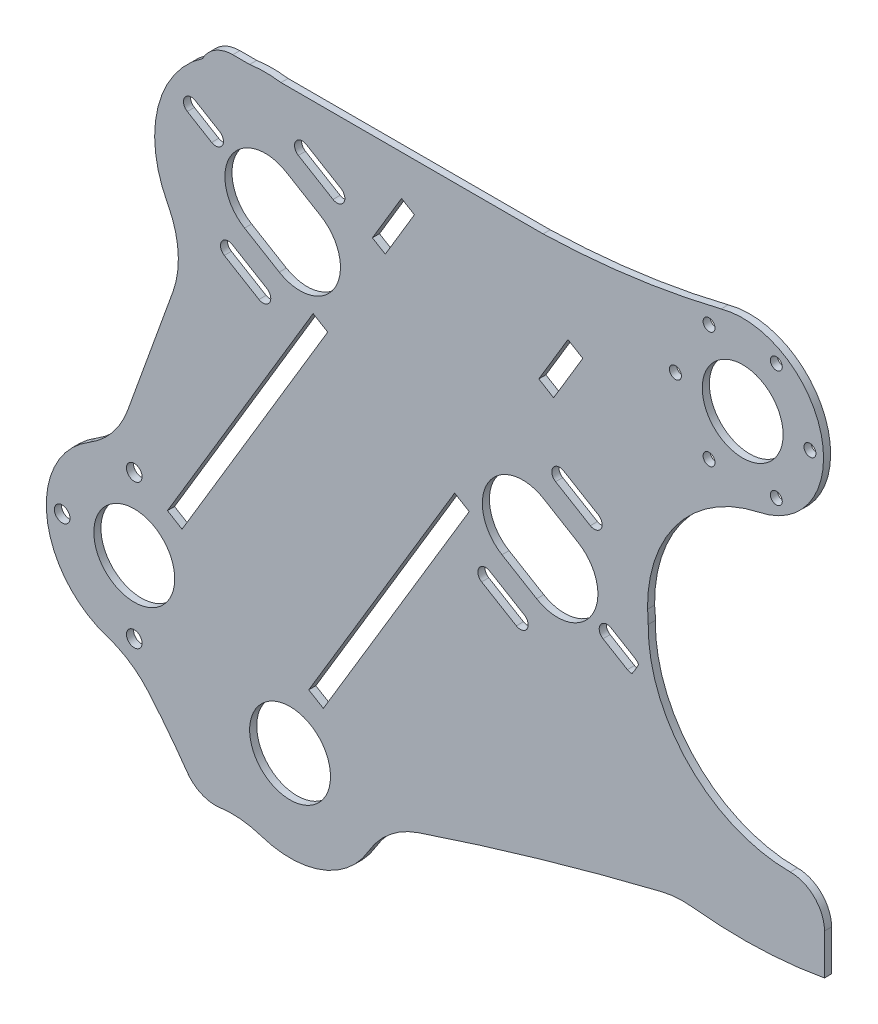
SolidWorks part; units mm, degrees
ref_plane "Plano frontal" through (0, 0, 0) normal (0, 0, 1) x (1, 0, 0)
ref_plane "Plano superior" through (0, 0, 0) normal (0, 1, 0) x (1, 0, 0)
ref_plane "Plano direito" through (0, 0, 0) normal (1, 0, 0) x (0, 0, -1)
sketch "Esboço1" plane through (0, 0, 0) normal (0, 0, 1) x (1, 0, 0)
  line L0 (49.9, 342) -> (-3.2758, 342)
  line L1 (49.9, 380) -> (-110.1, 380)
  line L3 (-3.2758, 342) -> (-3.2758, 208.9035)
  arc A0 (49.9, 342) -> (49.9, 380) centre (49.9, 361) ccw
  arc A1 (-110.1, 380) -> (-3.2758, 208.9035) centre (49.9, 361) ccw
  circle A2 centre (49.9, 361) radius 14.25
  dimension "D1" = 28.5
  dimension "D2" = 160
extrude "Ressalto-extrusão1" add sketch "Esboço1" along normal blind 2.5
sketch "Esboço2" plane through (0, 0, 2.5) normal (0, 0, 1) x (1, 0, 0)
  line L0 (-80.4635, 317.1268) -> (-48.9925, 362.4233)
  line L2 (-53.7045, 365.8323) -> (-85.3921, 320.5779)
  line L3 (-85.3921, 320.5779) -> (-80.4635, 317.1268)
  line L4 (49.9, 380) -> (-110.1, 380) construction
  line L5 (-53.7045, 365.8323) -> (-56.2781, 367.6942)
  line L6 (-56.2781, 367.6942) -> (-47.4451, 368.6891)
  line L7 (-47.4451, 368.6891) -> (-46.4607, 359.9499)
  line L8 (-46.4607, 359.9499) -> (-48.9925, 362.4233)
  line L9 (-51.3485, 364.1278) -> (-47.4451, 368.6891) construction
  line L10 (-53.7045, 365.8323) -> (-48.9925, 362.4233) construction
  dimension "D1" = 55
extrude "Corte-extrusão1" [suppressed] cut sketch "Esboço2" against normal blind 6
sketch "Esboço3" plane through (0, 0, 2.5) normal (0, 0, 1) x (1, 0, 0)
  line L0 (-3.2758, 208.9035) -> (-3.2758, 342) construction
  line L1 (78.7242, 230.9832) -> (78.7242, 202.475)
  line L2 (-3.2758, 208.9035) -> (-3.2758, 238.9035)
  arc A0 (-3.2758, 238.9035) -> (78.7242, 230.9832) centre (49.9, 361) ccw
  arc A1 (-3.2758, 208.9035) -> (78.7242, 202.475) centre (49.9, 361) ccw
  dimension "D1" = 82
  dimension "D2" = 30
extrude "Ressalto-extrusão2" add sketch "Esboço3" against normal blind 2.5
sketch "Esboço5" plane through (0, 0, 2.5) normal (0, 0, 1) x (1, 0, 0)
  line L0 (-110.1, 380) -> (-141.9313, 380)
  line L1 (-141.9313, 380) -> (-141.2627, 323.7246)
  line L2 (-186.8216, 197.6391) -> (-141.2627, 323.7246)
  line L7 (49.9, 380) -> (-110.1, 380)
  line L8 (78.7242, 202.475) -> (78.7242, 230.9832)
  line L9 (-3.2758, 238.9035) -> (-3.2758, 342)
  line L10 (-3.2758, 342) -> (49.9, 342)
  arc A0 (-186.8216, 197.6391) -> (-141.2627, 146.1998) centre (-333.9706, 21.4169) cw
  arc A2 (-141.2627, 146.1998) -> (27.0633, 201.5024) centre (279.6298, -851.0608) cw
  arc A3 (-110.1, 380) -> (78.7242, 202.475) centre (49.9, 361) ccw construction
  arc A7 (49.9, 342) -> (49.9, 380) centre (49.9, 361) ccw
  arc A8 (-110.1, 380) -> (78.7242, 202.475) centre (49.9, 361) ccw
  arc A9 (-3.2758, 238.9035) -> (78.7242, 230.9832) centre (49.9, 361) ccw
  arc A11 (-110.1, 380) -> (27.0633, 201.5024) centre (49.9, 361) ccw
  arc M10 (-110.1, 380) -> (78.7242, 202.475) centre (49.9, 361) ccw
  dimension "D1" = 0
extrude "Ressalto-extrusão3" add sketch "Esboço5" against normal blind 2.5 contours A0 A2 L0 L1 L2 M10 region at (-109.9694, 237.9744, 2.5)
sketch "Esboço6" plane through (0, 0, 2.5) normal (0, 0, 1) x (1, 0, 0)
  line L0 (-118.3294, 341.3928) -> (-15.3825, 279.7331) construction
  line L1 (-164.5132, 209.792) -> (-109.6082, 176.9068) construction
  line L2 (-66.8559, 310.563) -> (-137.0607, 193.3494) construction
  circle A0 centre (-118.3294, 341.3928) radius 14.25
  circle A1 centre (-15.3825, 279.7331) radius 14.25
  circle A2 centre (-164.5132, 209.792) radius 14.25
  circle A3 centre (-109.6082, 176.9068) radius 14.25
  dimension "D1" = 28.5
  dimension "D2" = 28.5
  dimension "D3" = 28.5
  dimension "D4" = 28.5
  dimension "D5" = 120
  dimension "D6" = 64
extrude "Corte-extrusão2" cut sketch "Esboço6" against normal through all
sketch "Esboço7" plane through (0, 0, 2.5) normal (0, 0, 1) x (1, 0, 0)
  line L0 (-164.5132, 209.792) -> (-109.6082, 176.9068) construction
  line L1 (-109.6082, 176.9068) -> (-37.0028, 298.1283) construction
  line L2 (-164.5132, 209.792) -> (-93.0231, 329.1516) construction
sketch "Esboço8" plane through (0, 0, 2.5) normal (0, 0, 1) x (1, 0, 0)
  circle A0 centre (-164.5132, 209.792) radius 24.626
  circle A1 centre (-164.5132, 209.792) radius 14.25
extrude "Ressalto-extrusão4" add sketch "Esboço8" against normal blind 2.5
fillet "Filete1" radius 12 1 edges at (-174.2585, 232.4077, 1.25)
fillet "Filete2" radius 12 3 edges at (-141.9313, 380, 1.25) (-141.2627, 323.7246, 1.25) (-3.2758, 238.9035, 1.25)
fillet "Filete3" radius 12 1 edges at (78.7242, 230.9832, 1.25)
fillet "Filete4" radius 12 1 edges at (-3.2758, 342, 1.25)
sketch "Esboço9" plane through (0, 0, 2.5) normal (0, 0, 1) x (1, 0, 0)
  circle A0 centre (-118.3294, 341.3928) radius 25.4 construction
  circle A1 centre (-164.5132, 209.792) radius 25.4 construction
  circle A2 centre (-118.3294, 341.3928) radius 39
  circle A3 centre (-164.5132, 209.792) radius 31
  circle A4 centre (-118.3294, 341.3928) radius 14.25
  circle A5 centre (-164.5132, 209.792) radius 14.25
  circle A7 centre (-118.3294, 341.3928) radius 14.25 construction
  dimension "D1" = 50.8
  dimension "D2" = 50.8
  dimension "D3" = 78
  dimension "D4" = 62
extrude "Ressalto-extrusão5" add sketch "Esboço9" against normal blind 2.5
sketch "Esboço10" plane through (0, 0, 2.5) normal (0, 0, 1) x (1, 0, 0)
  circle A0 centre (-164.5132, 209.792) radius 25.4 construction
  circle A6 centre (-189.9132, 209.792) radius 2.75
  circle A7 centre (-164.5132, 235.192) radius 2.75
  circle A8 centre (-139.1132, 209.792) radius 2.75
  circle A9 centre (-164.5132, 184.392) radius 2.75
  dimension "D1" = 50.8
extrude "Corte-extrusão3" cut sketch "Esboço10" against normal through all
sketch "Esboço11" plane through (0, 0, 2.5) normal (0, 0, 1) x (1, 0, 0)
  line L0 (-87.028, 319.847) -> (-48.9851, 297.4774) construction
  line L1 (-68.0065, 308.6622) -> (-136.137, 192.7962) construction
  line L2 (-164.5132, 209.792) -> (-109.6082, 176.9068) construction
  line L3 (-87.028, 319.847) -> (-155.9343, 204.6537)
  line L4 (-48.9851, 297.4774) -> (-118.1871, 182.0451)
  circle A0 centre (-118.3294, 341.3928) radius 38 construction
  circle A1 centre (-15.3825, 279.7331) radius 38 construction
  circle A2 centre (-164.5132, 209.792) radius 10
  circle A3 centre (-109.6082, 176.9068) radius 10
  dimension "D1" = 76
  dimension "D2" = 76
  dimension "D3" = 20
  dimension "D4" = 20
sketch "Esboço12" plane through (0, 0, 2.5) normal (0, 0, 1) x (1, 0, 0)
  circle A0 centre (-109.6082, 176.9068) radius 32
  circle A1 centre (-109.6082, 176.9068) radius 14.25
  circle A2 centre (-15.3825, 279.7331) radius 32
  circle A3 centre (-15.3825, 279.7331) radius 14.25
  dimension "D1" = 64
  dimension "D2" = 64
extrude "Ressalto-extrusão6" add sketch "Esboço12" against normal blind 2.5
sketch "Esboço13" plane through (0, 0, 2.5) normal (0, 0, 1) x (1, 0, 0)
  line L0 (-144.2405, 224.2027) -> (-92.9058, 310.0208) construction
  line L1 (-144.2405, 224.2027) -> (-147.6732, 226.256) construction
  line L2 (-92.9058, 310.0208) -> (-96.3386, 312.0742) construction
  line L3 (-147.6732, 226.256) -> (-96.3386, 312.0742) construction
  line L4 (-87.028, 319.847) -> (-155.9343, 204.6537) construction
  line L5 (-55.0433, 287.3721) -> (-106.4615, 201.604) construction
  line L6 (-55.0433, 287.3721) -> (-51.6125, 285.3154) construction
  line L7 (-106.4615, 201.604) -> (-103.0307, 199.5473) construction
  line L8 (-51.6125, 285.3154) -> (-103.0307, 199.5473) construction
  line L9 (-48.9851, 297.4774) -> (-118.1871, 182.0451) construction
  line L10 (-144.2405, 224.2027) -> (-106.4615, 201.604) construction
  line L11 (-96.3386, 312.0742) -> (-147.6732, 226.256)
  line L12 (-96.3386, 312.0742) -> (-101.4877, 315.1543)
  line L13 (-147.6732, 226.256) -> (-152.8223, 229.3361)
  line L14 (-101.4877, 315.1543) -> (-152.8223, 229.3361)
  line L15 (-103.0307, 199.5473) -> (-51.6125, 285.3154)
  line L16 (-103.0307, 199.5473) -> (-97.8846, 196.4622)
  line L17 (-51.6125, 285.3154) -> (-46.4664, 282.2303)
  line L18 (-97.8846, 196.4622) -> (-46.4664, 282.2303)
  dimension "D1" = 100
  dimension "D2" = 100
  dimension "D3" = 4
  dimension "D4" = 4
  dimension "D5" = 6
  dimension "D6" = 6
extrude "Corte-extrusão4" cut sketch "Esboço13" against normal blind 6
sketch "Esboço14" plane through (0, 0, 2.5) normal (0, 0, 1) x (1, 0, 0)
  circle A0 centre (-139.1132, 209.792) radius 2.75
extrude "Ressalto-extrusão7" add sketch "Esboço14" against normal blind 2.5
sketch "Esboço15" plane through (0, 0, 0) normal (0, 0, -1) x (-1, 0, 0)
  line L0 (6.4459, 348.9866) -> (16.7295, 331.8329)
  line L1 (6.4459, 348.9866) -> (11.6764, 352.1222)
  line L2 (16.7295, 331.8329) -> (21.96, 334.9686)
  line L3 (11.6764, 352.1222) -> (21.96, 334.9686)
  line L4 (65.7809, 363.1587) -> (76.0478, 345.995)
  line L5 (65.7809, 363.1587) -> (70.3295, 365.8796)
  line L6 (76.0478, 345.995) -> (80.5964, 348.7159)
  line L7 (70.3295, 365.8796) -> (80.5964, 348.7159)
extrude "Corte-extrusão5" cut sketch "Esboço15" against normal blind 10
sketch "Esboço16" plane through (0, 0, 2.5) normal (0, 0, 1) x (1, 0, 0)
  circle A0 centre (49.9, 361) radius 28.5
  circle A1 centre (49.9, 361) radius 14.25
  dimension "D1" = 57
extrude "Ressalto-extrusão8" add sketch "Esboço16" against normal blind 2.5
fillet "Filete6" radius 12 2 edges at (28.6574, 342, 1.25) (28.6574, 380, 1.25)
sketch "Esboço17" plane through (0, 0, 0) normal (0, 0, -1) x (-1, 0, 0)
  circle A0 centre (15.3825, 279.7331) radius 25.4 construction
  circle A1 centre (118.3294, 341.3928) radius 25.4 construction
  circle A2 centre (15.3825, 305.1331) radius 2.75
  circle A3 centre (-10.0175, 279.7331) radius 2.75
  circle A4 centre (15.3825, 254.3331) radius 2.75
  circle A5 centre (40.7825, 279.7331) radius 2.75
  circle A6 centre (118.3294, 366.7928) radius 2.75
  circle A7 centre (92.9294, 341.3928) radius 2.75
  circle A8 centre (118.3294, 315.9928) radius 2.75
  circle A9 centre (143.7294, 341.3928) radius 2.75
  dimension "D1" = 50.8
  dimension "D2" = 50.8
  dimension "D3" = 5.5
  dimension "D4" = 5.5
  dimension "D5" = 5.5
  dimension "D6" = 5.5
  dimension "D7" = 5.5
extrude "Corte-extrusão6" [suppressed] cut sketch "Esboço17" against normal blind 2.5
fillet "Filete7" radius 32 6 edges at (27.0633, 201.5024, 1.25) (-78.255, 170.5054, 1.25) (-128.8584, 151.3446, 1.25) (-166.9045, 178.8844, 1.25) (-171.5187, 239.9901, 1.25) (-145.1196, 313.0506, 1.25)
fillet "Filete8" radius 12 1 edges at (-3.2758, 250.1117, 1.25)
fillet "Filete9" radius 12 1 edges at (-3.2758, 309.3545, 1.25)
fillet "Filete10" radius 12 1 edges at (-141.2627, 146.1998, 1.25)
sketch "Esboço18" plane through (0, 0, 2.5) normal (0, 0, 1) x (1, 0, 0)
  circle A0 centre (38.05, 381.5248) radius 2.1
  circle A1 centre (61.75, 381.5248) radius 2.1
  circle A2 centre (73.6, 361) radius 2.1
  circle A3 centre (26.2, 361) radius 2.1
  circle A4 centre (38.05, 340.4752) radius 2.1
  circle A5 centre (61.75, 340.4752) radius 2.1
extrude "Corte-extrusão7" cut sketch "Esboço18" against normal through all
sketch "Esboço19" plane through (0, 0, 2.5) normal (0, 0, 1) x (1, 0, 0)
  line L0 (-118.3294, 341.3928) -> (-15.3825, 279.7331) construction
  line L1 (-118.3294, 341.3928) -> (-106.1044, 334.0707) construction
  line L2 (-111.0073, 353.6178) -> (-98.7823, 346.2957)
  line L3 (-125.6515, 329.1679) -> (-113.4265, 321.8458)
  line L4 (-15.3825, 279.7331) -> (-27.6074, 287.0552) construction
  line L5 (-22.7046, 267.5081) -> (-34.9295, 274.8302)
  line L6 (-8.0604, 291.958) -> (-20.2853, 299.2801)
  circle A0 centre (-118.3294, 341.3928) radius 14.25 construction
  arc A1 (-111.0073, 353.6178) -> (-125.6515, 329.1679) centre (-118.3294, 341.3928) ccw
  arc A2 (-113.4265, 321.8458) -> (-98.7823, 346.2957) centre (-106.1044, 334.0707) ccw
  circle A3 centre (-15.3825, 279.7331) radius 14.25 construction
  arc A4 (-22.7046, 267.5081) -> (-8.0604, 291.958) centre (-15.3825, 279.7331) ccw
  arc A5 (-20.2853, 299.2801) -> (-34.9295, 274.8302) centre (-27.6074, 287.0552) ccw
  point P4 (-112.2169, 337.7318)
  point P12 (-21.4949, 283.3941)
extrude "Corte-extrusão8" cut sketch "Esboço19" against normal blind 10
sketch "Esboço21" plane through (0, 0, 2.5) normal (0, 0, 1) x (1, 0, 0)
  arc A0 (16.6148, 279.3142) -> (66.6745, 228.8045) centre (66.468, 278.6615) ccw
  arc A1 (1.4429, 252.5134) -> (2.1497, 306.5029) centre (-15.3825, 279.7331) ccw construction
  arc A2 (78.7242, 216.8046) -> (65.3336, 228.7237) centre (66.7242, 216.8046) ccw construction
  arc A3 (1.4429, 252.5134) -> (16.6148, 279.3142) centre (-15.3825, 279.7331) ccw
  arc A4 (1.4429, 252.5134) -> (4.6466, 235.7509) centre (1.3973, 243.8173) ccw
  arc A5 (4.6466, 235.7509) -> (66.6745, 228.8045) centre (45.9194, 323.8842) ccw
sketch "Esboço20" plane through (0, 0, 2.5) normal (0, 0, 1) x (1, 0, 0)
  line L0 (-118.3294, 341.3928) -> (-106.1044, 334.0707) construction
  line L1 (-105.2781, 363.1833) -> (-93.0531, 355.8612) construction
  line L2 (-131.3807, 319.6024) -> (-119.1558, 312.2803) construction
  line L3 (-105.2781, 363.1833) -> (-93.0531, 355.8612) construction
  line L4 (-103.865, 365.5425) -> (-91.6401, 358.2204)
  line L5 (-106.6911, 360.8241) -> (-94.4662, 353.502)
  line L6 (-144.4093, 357.0133) -> (-135.8304, 351.875) construction
  line L7 (-142.9962, 359.3725) -> (-134.4173, 354.2342)
  line L8 (-145.8223, 354.6541) -> (-137.2434, 349.5158)
  line L9 (-131.3807, 319.6024) -> (-119.1558, 312.2803) construction
  line L10 (-129.9677, 321.9616) -> (-117.7427, 314.6395)
  line L11 (-132.7937, 317.2432) -> (-120.5688, 309.9211)
  line L12 (-122.0059, 269.1651) -> (-77.3216, 242.4313) construction
  line L13 (-147.6732, 226.256) -> (-96.3386, 312.0742) construction
  line L14 (-51.6125, 285.3154) -> (-103.0307, 199.5473) construction
  line L15 (-99.6638, 255.7982) -> (-73.9869, 298.7159) construction
  line L16 (10.6794, 264.2266) -> (2.0955, 269.3565) construction
  line L17 (12.0902, 266.5872) -> (3.5062, 271.7171)
  line L18 (9.2687, 261.866) -> (0.6848, 266.9959)
  line L19 (-28.4457, 258.0183) -> (-40.6778, 265.3284) construction
  line L20 (-27.035, 260.3789) -> (-39.2671, 267.689)
  line L21 (-29.8564, 255.6577) -> (-42.0886, 262.9678)
  line L22 (-2.3858, 301.6247) -> (-14.6179, 308.9348) construction
  line L23 (-0.9751, 303.9853) -> (-13.2072, 311.2954)
  line L24 (-3.7965, 299.2641) -> (-16.0286, 306.5742)
  arc A1 (-105.2781, 363.1833) -> (-131.3807, 319.6024) centre (-118.3294, 341.3928) ccw construction
  arc A2 (-119.1558, 312.2803) -> (-93.0531, 355.8612) centre (-106.1044, 334.0707) ccw construction
  arc A4 (-103.865, 365.5425) -> (-106.6911, 360.8241) centre (-105.2781, 363.1833) ccw
  arc A5 (-94.4662, 353.502) -> (-91.6401, 358.2204) centre (-93.0531, 355.8612) ccw
  arc A6 (-142.9962, 359.3725) -> (-145.8223, 354.6541) centre (-144.4093, 357.0133) ccw
  arc A7 (-137.2434, 349.5158) -> (-134.4173, 354.2342) centre (-135.8304, 351.875) ccw
  arc A8 (-129.9677, 321.9616) -> (-132.7937, 317.2432) centre (-131.3807, 319.6024) ccw
  arc A9 (-120.5688, 309.9211) -> (-117.7427, 314.6395) centre (-119.1558, 312.2803) ccw
  arc A10 (12.0902, 266.5872) -> (9.2687, 261.866) centre (10.6794, 264.2266) cw
  arc A11 (0.6848, 266.9959) -> (3.5062, 271.7171) centre (2.0955, 269.3565) cw
  arc A12 (-27.035, 260.3789) -> (-29.8564, 255.6577) centre (-28.4457, 258.0183) cw
  arc A13 (-42.0886, 262.9678) -> (-39.2671, 267.689) centre (-40.6778, 265.3284) cw
  arc A14 (-0.9751, 303.9853) -> (-3.7965, 299.2641) centre (-2.3858, 301.6247) cw
  arc A15 (-16.0286, 306.5742) -> (-13.2072, 311.2954) centre (-14.6179, 308.9348) cw
  point P3 (-112.2169, 337.7318)
  point P12 (-99.1656, 359.5222)
  point P17 (-140.1198, 354.4442)
  point P26 (-125.2682, 315.9414)
  point P41 (6.3875, 266.7915)
  point P48 (-34.5618, 261.6733)
  point P55 (-8.5019, 305.2798)
  dimension "D1" = 25.4
  dimension "D2" = 2.75
  dimension "D4" = 2.75
  dimension "D5" = 2.75
  dimension "D3" = 10
extrude "Corte-extrusão9" cut sketch "Esboço20" against normal blind 10
extrude "Ressalto-extrusão9" add sketch "Esboço21" against normal blind 2.5
sketch "Esboço22" plane through (0, 0, 0) normal (0, 0, 1) x (1, 0, 0)
  line L0 (-118.3294, 341.3928) -> (-106.1044, 334.0707) construction
  line L1 (-105.2781, 363.1833) -> (-93.0531, 355.8612) construction
  line L2 (-131.3807, 319.6024) -> (-119.1558, 312.2803) construction
  line L3 (-105.2781, 363.1833) -> (-93.0531, 355.8612) construction
  line L4 (-103.865, 365.5425) -> (-91.6401, 358.2204)
  line L5 (-106.6911, 360.8241) -> (-94.4662, 353.502)
  line L6 (-144.4093, 357.0133) -> (-135.8304, 351.875) construction
  line L7 (-142.9962, 359.3725) -> (-134.4173, 354.2342)
  line L8 (-145.8223, 354.6541) -> (-137.2434, 349.5158)
  line L9 (-131.3807, 319.6024) -> (-119.1558, 312.2803) construction
  line L10 (-129.9677, 321.9616) -> (-117.7427, 314.6395)
  line L11 (-132.7937, 317.2432) -> (-120.5688, 309.9211)
  line L12 (-122.0059, 269.1651) -> (-77.3216, 242.4313) construction
  line L15 (-99.6638, 255.7982) -> (-73.9869, 298.7159) construction
  line L16 (10.6794, 264.2266) -> (2.0955, 269.3565) construction
  line L17 (12.0902, 266.5872) -> (3.5062, 271.7171)
  line L18 (9.2687, 261.866) -> (0.6848, 266.9959)
  line L19 (-28.4457, 258.0183) -> (-40.6778, 265.3284) construction
  line L20 (-27.035, 260.3789) -> (-39.2671, 267.689)
  line L21 (-29.8564, 255.6577) -> (-42.0886, 262.9678)
  line L22 (-2.3858, 301.6247) -> (-14.6179, 308.9348) construction
  line L23 (-0.9751, 303.9853) -> (-13.2072, 311.2954)
  line L24 (-3.7965, 299.2641) -> (-16.0286, 306.5742)
  arc A1 (-105.2781, 363.1833) -> (-131.3807, 319.6024) centre (-118.3294, 341.3928) ccw construction
  arc A2 (-119.1558, 312.2803) -> (-93.0531, 355.8612) centre (-106.1044, 334.0707) ccw construction
  arc A4 (-103.865, 365.5425) -> (-106.6911, 360.8241) centre (-105.2781, 363.1833) ccw
  arc A5 (-94.4662, 353.502) -> (-91.6401, 358.2204) centre (-93.0531, 355.8612) ccw
  arc A6 (-142.9962, 359.3725) -> (-145.8223, 354.6541) centre (-144.4093, 357.0133) ccw
  arc A7 (-137.2434, 349.5158) -> (-134.4173, 354.2342) centre (-135.8304, 351.875) ccw
  arc A8 (-129.9677, 321.9616) -> (-132.7937, 317.2432) centre (-131.3807, 319.6024) ccw
  arc A9 (-120.5688, 309.9211) -> (-117.7427, 314.6395) centre (-119.1558, 312.2803) ccw
  arc A10 (12.0902, 266.5872) -> (9.2687, 261.866) centre (10.6794, 264.2266) cw
  arc A11 (0.6848, 266.9959) -> (3.5062, 271.7171) centre (2.0955, 269.3565) cw
  arc A12 (-27.035, 260.3789) -> (-29.8564, 255.6577) centre (-28.4457, 258.0183) cw
  arc A13 (-42.0886, 262.9678) -> (-39.2671, 267.689) centre (-40.6778, 265.3284) cw
  arc A14 (-0.9751, 303.9853) -> (-3.7965, 299.2641) centre (-2.3858, 301.6247) cw
  arc A15 (-16.0286, 306.5742) -> (-13.2072, 311.2954) centre (-14.6179, 308.9348) cw
  point P3 (-112.2169, 337.7318)
  point P12 (-99.1656, 359.5222)
  point P17 (-140.1198, 354.4442)
  point P26 (-125.2682, 315.9414)
  point P41 (6.3875, 266.7915)
  point P48 (-34.5618, 261.6733)
  point P55 (-8.5019, 305.2798)
  dimension "D1" = 25.4
  dimension "D2" = 2.75
  dimension "D4" = 2.75
  dimension "D5" = 2.75
  dimension "D3" = 10
sketch "Esboço23" plane through (0, 0, 2.5) normal (0, 0, 1) x (1, 0, 0)
  line L0 (23.8376, 380) -> (-112.8078, 380) construction
  line L1 (-20.4278, 380) -> (23.8376, 380)
  arc A0 (42.301, 388.4683) -> (-20.4278, 380) centre (-28.763, 678.3095) cw
  arc A2 (31.5598, 339.1852) -> (31.5598, 382.8148) centre (49.9, 361) ccw construction
  arc A3 (23.8376, 380) -> (31.5598, 382.8148) centre (23.8376, 392) ccw
  arc A4 (31.5598, 382.8148) -> (42.301, 388.4683) centre (49.9, 361) cw
extrude "Ressalto-extrusão10" add sketch "Esboço23" against normal blind 2.5
sketch "Esboço24" plane through (0, 0, 2.5) normal (0, 0, 1) x (1, 0, 0)
  line L6 (-20.4278, 380) -> (-112.8078, 380)
  line L7 (-123.851, 380) -> (-129.7878, 380)
  line L8 (-150.8807, 297.1063) -> (-166.8421, 252.9328)
  line L9 (78.7242, 202.475) -> (78.7242, 216.8046)
  line L10 (-3.2758, 316.5416) -> (-3.2758, 330)
  line L11 (8.7242, 342) -> (23.8376, 342)
  line L16 (-3.2758, 316.5416) -> (-3.2758, 330)
  line L17 (8.7242, 342) -> (23.8376, 342)
  arc A0 (55.8063, 333.1187) -> (16.6148, 279.3142) centre (66.1203, 284.4301) ccw
  arc A2 (31.5598, 339.1852) -> (42.301, 388.4683) centre (49.9, 361) ccw construction
  arc A26 (-20.4278, 380) -> (42.301, 388.4683) centre (-28.763, 678.3095) ccw
  arc A27 (-112.8078, 380) -> (-123.851, 380) centre (-118.3294, 341.3928) ccw
  arc A28 (-129.7878, 380) -> (-140.4449, 373.5161) centre (-129.7878, 368) ccw
  arc A29 (-140.4449, 373.5161) -> (-152.7411, 323.0398) centre (-118.3294, 341.3928) ccw
  arc A30 (-150.8807, 297.1063) -> (-152.7411, 323.0398) centre (-180.9763, 307.9809) ccw
  arc A31 (-180.4681, 236.371) -> (-166.8421, 252.9328) centre (-196.9377, 263.8073) ccw
  arc A32 (-180.4681, 236.371) -> (-174.0031, 180.2803) centre (-164.5132, 209.792) ccw
  arc A33 (-159.4774, 170.6121) -> (-174.0031, 180.2803) centre (-183.7991, 149.8166) ccw
  arc A34 (-145.8136, 152.9618) -> (-159.4774, 170.6121) centre (-333.9706, 21.4169) ccw
  arc A35 (-145.8136, 152.9618) -> (-134.3501, 147.9486) centre (-135.9788, 159.8375) ccw
  arc A36 (-119.8075, 146.5757) -> (-134.3501, 147.9486) centre (-130.0068, 116.2447) ccw
  arc A37 (-119.8075, 146.5757) -> (-81.8873, 160.9207) centre (-109.6082, 176.9068) ccw
  arc A38 (-64.335, 175.276) -> (-81.8873, 160.9207) centre (-54.1665, 144.9346) ccw
  arc A39 (21.2696, 200.0953) -> (-64.335, 175.276) centre (279.6298, -851.0608) ccw
  arc A40 (32.3858, 200.8305) -> (21.2696, 200.0953) centre (28.9075, 169.0202) ccw
  arc A41 (32.3858, 200.8305) -> (78.7242, 202.475) centre (49.9, 361) ccw
  arc A42 (78.7242, 216.8046) -> (66.6745, 228.8045) centre (66.7242, 216.8046) ccw
  arc A43 (16.6148, 279.3142) -> (66.6745, 228.8045) centre (66.468, 278.6615) ccw
  arc A44 (16.6148, 279.3142) -> (2.1497, 306.5029) centre (-15.3825, 279.7331) ccw
  arc A45 (-3.2758, 316.5416) -> (2.1497, 306.5029) centre (8.7242, 316.5416) ccw
  arc A46 (8.7242, 342) -> (-3.2758, 330) centre (8.7242, 330) ccw
  arc A47 (31.5598, 339.1852) -> (23.8376, 342) centre (23.8376, 330) ccw
  arc A48 (31.5598, 339.1852) -> (42.301, 388.4683) centre (49.9, 361) ccw
  arc A67 (16.6148, 279.3142) -> (2.1497, 306.5029) centre (-15.3825, 279.7331) ccw
  arc A68 (-3.2758, 316.5416) -> (2.1497, 306.5029) centre (8.7242, 316.5416) ccw
  arc A69 (8.7242, 342) -> (-3.2758, 330) centre (8.7242, 330) ccw
  arc A70 (31.5598, 339.1852) -> (23.8376, 342) centre (23.8376, 330) ccw
  arc A71 (31.5598, 339.1852) -> (55.8063, 333.1187) centre (49.9, 361) ccw
  dimension "D1" = 0
extrude "Ressalto-extrusão11" add sketch "Esboço24" against normal blind 2.5 contours A71 A70 L17 A69 L16 A68 A67 A0 region at (16.1972, 322.8986, 2.5)
ref_plane "Plano1" through (-96.3386, 312.0742, 2.5) normal (0.5133, 0.8582, 0) x (0.8582, -0.5133, 0)
sketch "Esboço26" plane through (0, 0, 2.5) normal (0, 0, 1) x (1, 0, 0)
  line L0 (-147.6732, 226.256) -> (-134.723, 226.256)
  line L1 (-134.723, 226.256) -> (-134.723, 247.9054)
  line L2 (-147.6732, 226.256) -> (-96.3386, 312.0742) construction
  line L3 (-134.723, 247.9054) -> (-147.6732, 226.256)
